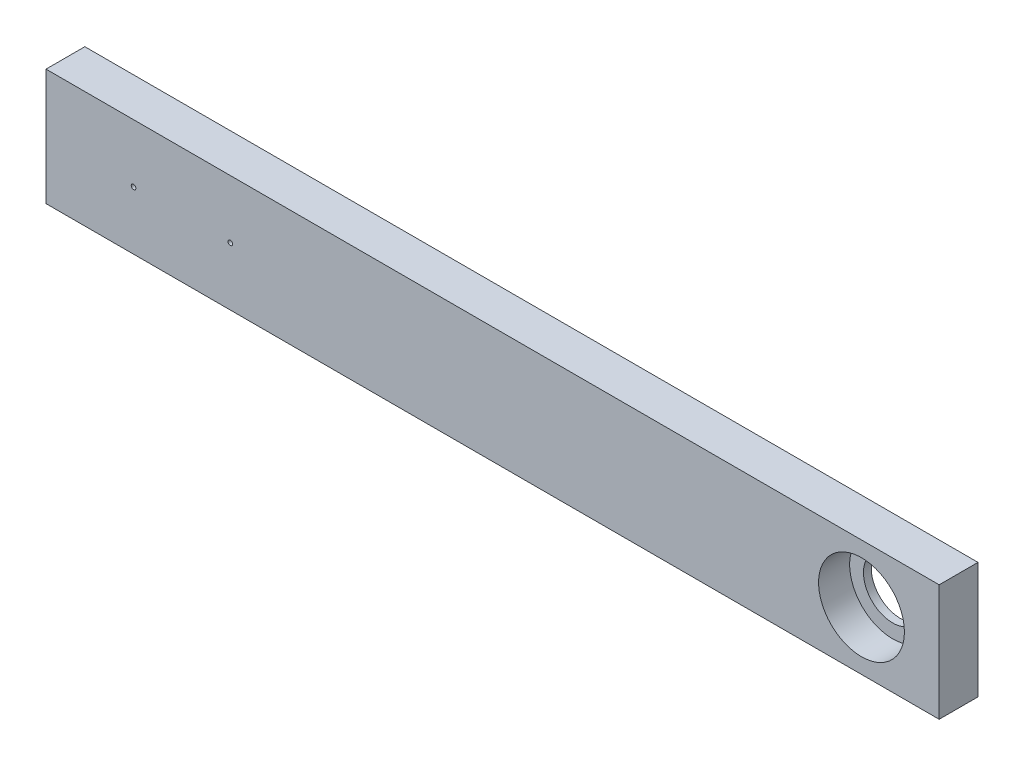
SolidWorks part; units mm, degrees
ref_plane "Front Plane" through (0, 0, 0) normal (0, 0, 1) x (1, 0, 0)
ref_plane "Top Plane" through (0, 0, 0) normal (0, 1, 0) x (1, 0, 0)
ref_plane "Right Plane" through (0, 0, 0) normal (1, 0, 0) x (0, 0, -1)
sketch "Sketch1" plane through (0, 0, 0) normal (0, 0, 1) x (1, 0, 0)
  line L0 (0, 15) -> (70, 15) construction
  line L1 (0, 30) -> (70, 30)
  line L2 (0, 30) -> (0, 0)
  line L3 (0, 0) -> (70, 0)
  line L4 (70, 30) -> (70, 0)
  line L5 (0, 30) -> (70, 0) construction
  line L6 (0, 0) -> (70, 30) construction
  line L7 (35, 30) -> (35, 0) construction
  line L9 (70, 30) -> (230, 30)
  line L10 (70, 30) -> (70, 0)
  line L11 (70, 0) -> (230, 0)
  line L12 (230, 30) -> (230, 0)
  line L24 (210, 30) -> (210, 0)
  circle A0 centre (22.55, 15) radius 0.6
  circle A3 centre (47.45, 15) radius 0.6
  circle A8 centre (210, 15) radius 11.05
  circle A9 centre (210, 15) radius 7.5
  point P0 (35, 15)
  point P11 (35, 0)
  point P22 (35, 15)
  dimension "D4" = 1.2
  dimension "D10" = 20
  dimension "D7" = 22.1
  dimension "D9" = 15
  dimension "D1" = 30
  dimension "D2" = 70
  dimension "D3" = 12.45
  dimension "D8" = 15
  dimension "D15" = 175
extrude "Boss-Extrude2" add sketch "Sketch1" along normal blind 10 contours L4 L1 L2 L3 A0 A3 | A8 L24 L9 L4 L11 | A8 L24 L11 L12 L9 region at (35, 15, 0) region at (136.8748, 15, 0) region at (222.4951, 15, 0)
extrude "Boss-Extrude3" add sketch "Sketch1<6>" along normal blind 2 contours A9 L24 A8 | A9 L24 A8 region at (217.6388, 22.6388, 0) region at (209.7529, 24.275, 0)
sketch "Sketch1<6>" plane through (0, 0, 0) normal (0, 0, 1) x (1, 0, 0) same geometry as "Sketch1"
